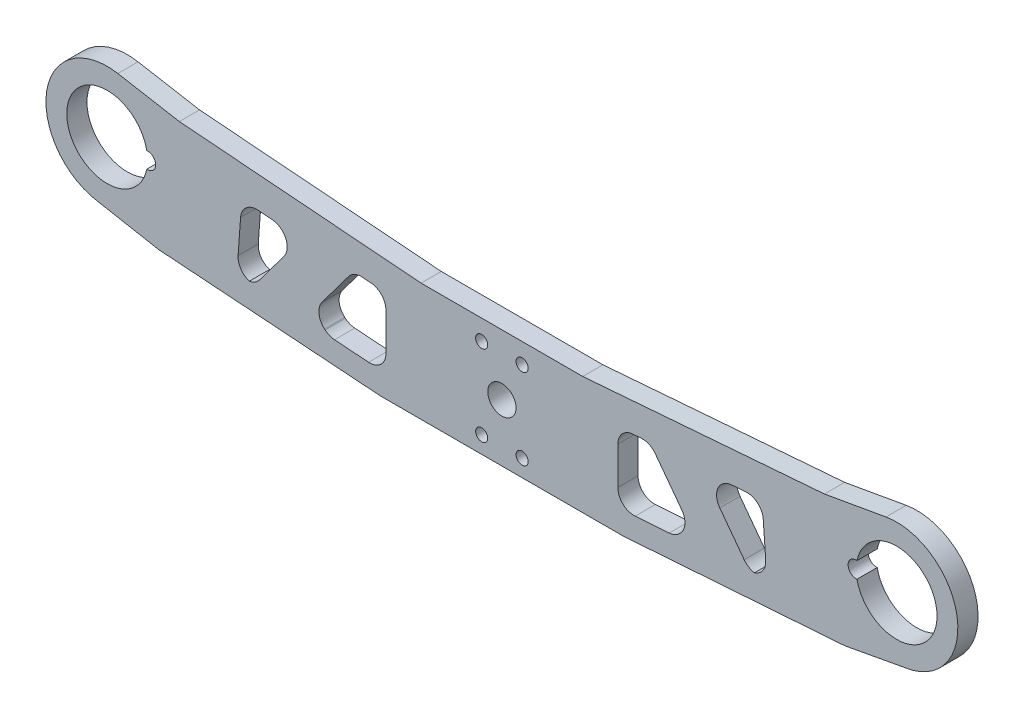
SolidWorks part; units mm, degrees
ref_plane "Ön Düzlem" through (0, 0, 0) normal (0, 0, 1) x (1, 0, 0)
ref_plane "Üst Düzlem" through (0, 0, 0) normal (0, 1, 0) x (1, 0, 0)
ref_plane "Sağ Düzlem" through (0, 0, 0) normal (1, 0, 0) x (0, 0, -1)
sketch "Çizim1" plane through (0, 0, 0) normal (0, 0, 1) x (1, 0, 0)
  line L1 (0, 15.0003) -> (20, 15.0003)
  line L2 (0, -14.2047) -> (30.0841, -14.2047)
  line L6 (79.8143, 19.7176) -> (95.0399, 22.4023)
  line L10 (84.9128, -10.2827) -> (99.9984, -7.4931)
  line L11 (20, 15.0003) -> (79.8143, 19.7176)
  line L12 (30.0841, -14.2047) -> (84.9128, -10.2827)
  line L23 (0, 15.0003) -> (0, 3.5)
  line L24 (0, 10.0003) -> (5, 10.0003)
  line L25 (0, -14.2047) -> (0, -3.5)
  line L26 (0, -10) -> (5, -10)
  arc A4 (95.0399, 22.4023) -> (99.9984, -7.4931) centre (97.6711, 7.4798) cw
  circle A16 centre (5, 10.0003) radius 1.5
  circle A17 centre (5, -10) radius 1.5
  arc A18 (0, -3.5) -> (0, 3.5) centre (0, 0) ccw
  dimension "D2" = 54.9689
  dimension "D3" = 20
  dimension "D1" = 15.3413
  dimension "D4" = 60
extrude "Yükseklik-Ekstrüzyon3" add sketch "Çizim1" along normal blind 5 contours L1 L11 L6 A4 L10 L12 L2 L25 A18 L23 | A17 | A16
sketch "Çizim2" plane through (0, 0, 0) normal (0, 0, 1) x (1, 0, 0)
  line L0 (28.6959, -8.7523) -> (42.7317, -7.7483)
  line L2 (28.6959, 8.5533) -> (28.6959, -8.7523)
  line L13 (49.5831, 9.5986) -> (61.257, -6.0359)
  line L15 (61.257, -6.0359) -> (65.5653, -5.7278)
  line L16 (65.5653, -5.7278) -> (64.376, 10.7652)
  line L17 (64.376, 10.7652) -> (49.5831, 9.5986)
  line L19 (36.6505, 9.1806) -> (28.6959, 8.5533)
  line L20 (42.7317, -7.7483) -> (46.7353, -4.3257)
  line L21 (46.7353, -4.3257) -> (36.6505, 9.1806)
  line L25 (30.0841, -14.2047) -> (84.9128, -10.2827) construction
  line L26 (20, 15.0003) -> (79.8143, 19.7176) construction
  arc A0 (87.8711, 5.4898) -> (87.8711, 9.4698) centre (97.6711, 7.4798) ccw
  arc A1 (87.8711, 9.4698) -> (87.8711, 5.4898) centre (87.6711, 7.4798) ccw
  arc A2 (87.8711, 5.4898) -> (87.8711, 9.4698) centre (97.6711, 7.4798) ccw
  dimension "D1" = 19.512
  dimension "D2" = 2
  dimension "D3" = 10
extrude "Kes-Ekstrüzyon3" cut sketch "Çizim2" along normal blind 16 contours A0 A1 | L16 L17 L13 L15 | L20 L21 L19 L2 L0 region at (35.7891, -0.5702, 0) region at (59.6083, 3.6224, 0) region at (97.4503, 7.4798, 0)
fillet "Radyus1" radius 4 9 edges at (28.6959, -8.7523, 2.5) (64.376, 10.7652, 2.5) (49.5831, 9.5986, 2.5) (65.5653, -5.7278, 2.5) (46.7353, -4.3257, 2.5) (36.6505, 9.1806, 2.5) (28.6959, 8.5533, 2.5) (42.7317, -7.7483, 2.5) (61.257, -6.0359, 2.5)
mirror "Aynalama1" about plane through (0, 0, 0) normal (1, 0, 0) of "Radyus1", "Yükseklik-Ekstrüzyon3", "Kes-Ekstrüzyon3"
